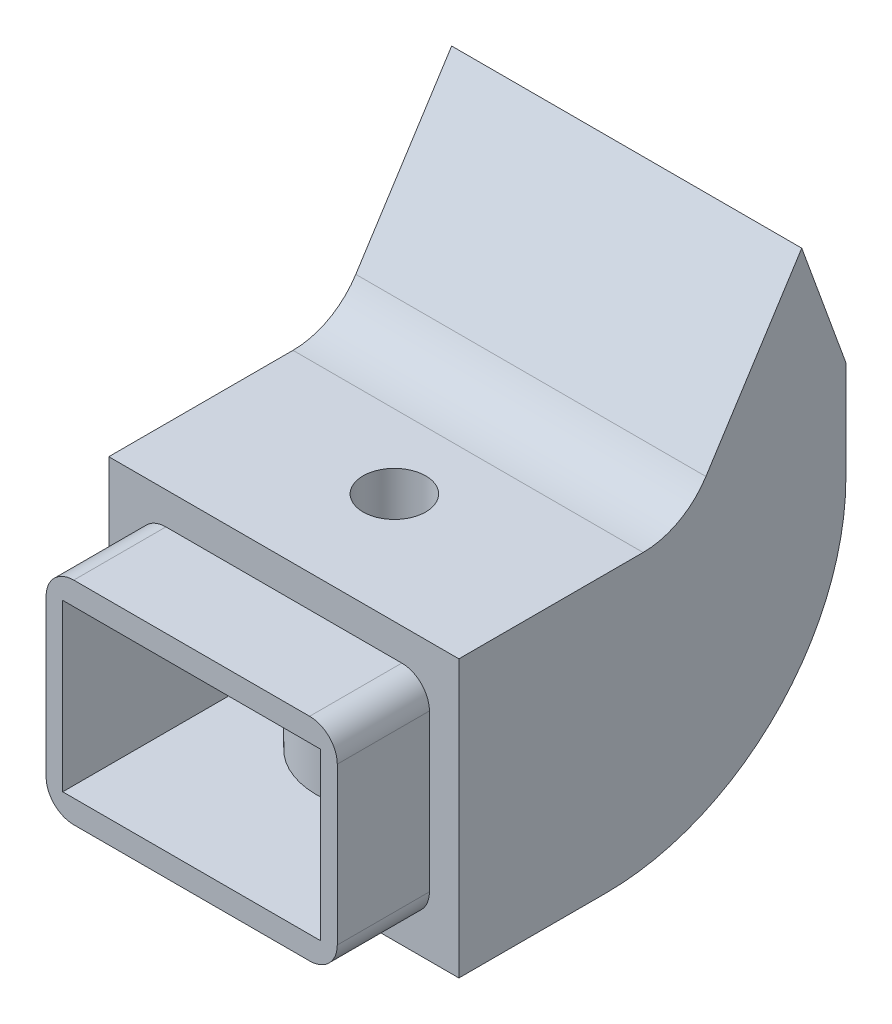
SolidWorks part; units mm, degrees
ref_plane "Alzado" through (0, 0, 0) normal (0, 0, 1) x (1, 0, 0)
ref_plane "Planta" through (0, 0, 0) normal (0, 1, 0) x (1, 0, 0)
ref_plane "Vista lateral" through (0, 0, 0) normal (1, 0, 0) x (0, 0, -1)
ref_plane "Plano1" through (7.9361, 0, 0) normal (1, 0, 0) x (0, 0, -1)
sketch "Croquis1" plane through (7.9361, 0, 0) normal (1, 0, 0) x (0, 0, -1)
  line L0 (-154.2857, -37.2136) -> (-128.2857, -37.2136)
  line L1 (-128.2857, -37.2136) -> (-128.2857, -33.7936)
  line L2 (-128.2857, -33.7936) -> (-137.0738, -9.6487)
  line L3 (-137.0738, -9.6487) -> (-149.2857, -9.6487)
  spline S0 degree 3 poles (-154.2857, -9.6487) (-152.6191, -9.6487) (-150.9524, -9.6487) (-149.2857, -9.6487) knots 0 0 0 0 1 1 1 1
  spline S1 degree 3 poles (-154.2857, -9.6487) (-154.2857, -18.837) (-154.2857, -28.0253) (-154.2857, -37.2136) knots 0 0 0 0 1 1 1 1
  dimension "D1" = 8.788
  dimension "D2" = 21
  dimension "D3" = 26
  dimension "D4" = 3.42
  dimension "D5" = 27.5649
extrude "Saliente-Extruir1" add sketch "Croquis1" against normal blind 18
sketch "Croquis2" plane through (0, -37.2136, 0) normal (0, -1, 0) x (1, 0, 0)
  line L0 (-10.0639, 154.2857) -> (7.9361, 154.2857)
  line L1 (7.9361, 149.2857) -> (7.9361, 128.2857)
  line L2 (7.9361, 128.2857) -> (-10.0639, 128.2857)
  line L3 (-10.0639, 128.2857) -> (-10.0639, 154.2857)
  line L4 (7.9361, 154.2857) -> (7.9361, 128.2857) construction
  spline S0 degree 3 poles (7.9361, 154.2857) (7.9361, 152.6191) (7.9361, 150.9524) (7.9361, 149.2857) knots 0 0 0 0 1 1 1 1
  dimension "D1" = 18
  dimension "D2" = 5
  dimension "D3" = 26
extrude "Saliente-Extruir2" add sketch "Croquis2" along normal blind 12
sketch "Croquis3" plane through (-10.0639, 0, 0) normal (-1, 0, 0) x (0, 0, 1)
  line L0 (135.0785, -49.2136) -> (137.8109, -49.2136)
  line L1 (137.8109, -49.2136) -> (137.8109, -40.2136)
  line L2 (137.8109, -40.2136) -> (130.2514, -28.3931)
  line L3 (130.2514, -28.3931) -> (129.3486, -30.8735)
  line L4 (129.3486, -30.8735) -> (135.0785, -49.2136)
  line L6 (137.0738, -9.6487) -> (149.2857, -9.6487) construction
  dimension "D1" = 16.4749
  dimension "D2" = 19.2073
  dimension "D3" = 24.0344
  dimension "D4" = 24.9371
  dimension "D5" = 18.7444
  dimension "D6" = 21.2248
  dimension "D7" = 30.5649
  dimension "D8" = 39.5649
extrude "Cortar-Extruir1" cut sketch "Croquis3" against normal blind 17
sketch "Croquis4" plane through (-10.0639, 0, 0) normal (-1, 0, 0) x (0, 0, 1)
  line L0 (137.8109, -49.2136) -> (154.2857, -49.2136)
  line L1 (154.2857, -49.2136) -> (154.2857, -40.2136)
  line L2 (154.2857, -40.2136) -> (137.8109, -40.2136)
  line L3 (137.8109, -40.2136) -> (137.8109, -49.2136)
  line L4 (154.2857, -49.2136) -> (137.8109, -49.2136) construction
  dimension "D1" = 16.4749
  dimension "D2" = 9
extrude "Cortar-Extruir2" cut sketch "Croquis4" against normal blind 15.5
sketch "Croquis5" plane through (0, 0, 154.2857) normal (0, 0, 1) x (1, 0, 0)
  line L0 (-10.0639, -40.2136) -> (-9.4639, -40.2136)
  line L1 (-9.4639, -40.2136) -> (-9.4639, -38.9636)
  line L2 (-9.4639, -38.9636) -> (6.3361, -38.9636)
  line L3 (6.3361, -38.9636) -> (6.3361, -49.2136)
  line L4 (6.3361, -49.2136) -> (7.9361, -49.2136)
  line L5 (7.9361, -49.2136) -> (7.9361, -37.2136)
  line L6 (7.9361, -9.6487) -> (-10.0639, -9.6487)
  line L7 (-10.0639, -37.2136) -> (-10.0639, -40.2136)
  line L8 (7.9361, -49.2136) -> (7.9361, -37.2136) construction
  line L9 (7.9361, -49.2136) -> (5.4361, -49.2136) construction
  spline S0 degree 3 poles (7.9361, -9.6487) (7.9361, -18.837) (7.9361, -28.0253) (7.9361, -37.2136) knots 0 0 0 0 1 1 1 1
  spline S1 degree 3 poles (-10.0639, -9.6487) (-10.0639, -18.837) (-10.0639, -28.0253) (-10.0639, -37.2136) knots 0 0 0 0 1 1 1 1
  dimension "D1" = 1.6
  dimension "D2" = 17.4
  dimension "D3" = 18
  dimension "D4" = 9
  dimension "D5" = 10.25
  dimension "D6" = 12
  dimension "D7" = 39.5649
extrude "Cortar-Extruir3" cut sketch "Croquis5" against normal blind 5
sketch "Croquis6" plane through (0, -9.6487, 0) normal (0, 1, 0) x (-1, 0, 0)
  line L0 (-7.9361, 137.0738) -> (10.0639, 137.0738)
  line L1 (10.0639, 137.0738) -> (10.0639, 149.2857)
  line L2 (10.0639, 149.2857) -> (-7.9361, 149.2857)
  line L3 (-7.9361, 149.2857) -> (-7.9361, 137.0738)
  line L4 (-7.9361, 137.0738) -> (-7.9361, 149.2857) construction
  line L5 (-7.9361, 149.2857) -> (10.0639, 149.2857) construction
  dimension "D1" = 18
  dimension "D2" = 12.212
extrude "Cortar-Extruir4" cut sketch "Croquis6" against normal blind 27.5649
sketch "Croquis7" plane through (0, -40.2136, 0) normal (0, -1, 0) x (1, 0, 0)
  line L0 (-9.4639, 154.2857) -> (-8.5639, 154.2857)
  line L1 (-8.5639, 154.2857) -> (-8.5639, 137.8109)
  line L2 (-8.5639, 137.8109) -> (-10.0639, 137.8109)
  line L3 (-10.0639, 137.8109) -> (-10.0639, 149.2857)
  line L4 (-10.0639, 149.2857) -> (-9.4639, 149.2857)
  line L5 (-9.4639, 149.2857) -> (-9.4639, 154.2857)
  line L6 (-9.4639, 149.2857) -> (-9.4639, 154.2857) construction
  line L7 (5.4361, 154.2857) -> (-9.4639, 154.2857) construction
  dimension "D1" = 0.9
  dimension "D2" = 0.6
  dimension "D3" = 5
  dimension "D4" = 16.4749
extrude "Saliente-Extruir3" add sketch "Croquis7" along normal blind 9
sketch "Croquis8" plane through (0, -49.2136, 0) normal (0, -1, 0) x (1, 0, 0)
  line L0 (-9.4639, 154.2857) -> (6.3361, 154.2857)
  line L1 (6.3361, 154.2857) -> (6.3361, 149.2857)
  line L2 (6.3361, 149.2857) -> (7.9361, 149.2857)
  line L3 (7.9361, 149.2857) -> (7.9361, 128.2857)
  line L4 (7.9361, 128.2857) -> (-10.0639, 128.2857)
  line L5 (-10.0639, 128.2857) -> (-10.0639, 149.2857)
  line L6 (-10.0639, 149.2857) -> (-9.4639, 149.2857)
  line L7 (-9.4639, 149.2857) -> (-9.4639, 154.2857)
  line L8 (5.4361, 137.8109) -> (5.4361, 154.2857) construction
  line L9 (6.9361, 137.8109) -> (5.4361, 137.8109) construction
  dimension "D1" = 0.9
  dimension "D2" = 2.5
  dimension "D3" = 14.9
  dimension "D4" = 15.5
  dimension "D5" = 11.4749
  dimension "D6" = 16.4749
  dimension "D7" = 9.5251
extrude "Saliente-Extruir4" add sketch "Croquis8" along normal blind 1.25
sketch "Croquis9" plane through (0, -50.4636, 0) normal (0, -1, 0) x (1, 0, 0)
  line L0 (-10.0639, 128.2857) -> (-10.0639, 149.2857)
  line L1 (-10.0639, 149.2857) -> (7.9361, 149.2857)
  line L2 (7.9361, 149.2857) -> (7.9361, 128.2857)
  line L3 (7.9361, 128.2857) -> (-10.0639, 128.2857)
  line L4 (-10.0639, 149.2857) -> (-10.0639, 128.2857) construction
  line L5 (-9.4639, 149.2857) -> (-10.0639, 149.2857) construction
  dimension "D1" = 18
  dimension "D2" = 21
extrude "Saliente-Extruir5" add sketch "Croquis9" along normal blind 1.75
sketch "Croquis10" plane through (0, 0, 137.8109) normal (0, 0, -1) x (-1, 0, 0)
  line L0 (-6.9361, -49.2136) -> (-5.4361, -49.2136)
  line L1 (-5.4361, -49.2136) -> (-5.4361, -40.2136)
  line L2 (-5.4361, -40.2136) -> (-6.9361, -40.2136)
  line L3 (-6.9361, -40.2136) -> (-6.9361, -49.2136)
  line L4 (-5.4361, -40.2136) -> (-5.4361, -49.2136) construction
  line L5 (-6.9361, -40.2136) -> (-5.4361, -40.2136) construction
  dimension "D1" = 1.5
  dimension "D2" = 9
extrude "Cortar-Extruir5" cut sketch "Croquis10" against normal blind 6.4749
sketch "Croquis11" plane through (0, 0, 137.8109) normal (0, 0, -1) x (-1, 0, 0)
  line L0 (8.5639, -49.2136) -> (10.0639, -49.2136)
  line L1 (10.0639, -49.2136) -> (10.0639, -40.2136)
  line L2 (10.0639, -40.2136) -> (8.5639, -40.2136)
  line L3 (8.5639, -40.2136) -> (8.5639, -49.2136)
  line L4 (8.5639, -49.2136) -> (8.5639, -40.2136) construction
  line L5 (10.0639, -40.2136) -> (8.5639, -40.2136) construction
  dimension "D1" = 1.5
  dimension "D2" = 9
extrude "Cortar-Extruir6" cut sketch "Croquis11" against normal blind 6.4749
sketch "Croquis12" plane through (-10.0639, 0, 0) normal (-1, 0, 0) x (0, 0, 1)
  line L0 (149.2857, -52.2136) -> (128.2857, -52.2136)
  line L1 (128.2857, -52.2136) -> (128.2857, -33.7936)
  line L2 (128.2857, -33.7936) -> (137.0738, -9.6487)
  line L3 (137.0738, -9.6487) -> (137.0738, -37.2136)
  line L4 (137.0738, -37.2136) -> (149.2857, -37.2136)
  line L5 (149.2857, -37.2136) -> (149.2857, -52.2136)
  line L7 (144.2857, -49.2136) -> (135.0785, -49.2136) construction
  dimension "D1" = 8.788
  dimension "D2" = 21
  dimension "D3" = 12
  dimension "D4" = 15.42
  dimension "D5" = 39.5649
  dimension "D6" = 3
extrude "Saliente-Extruir6" add sketch "Croquis12" along normal blind 1
draft "Ángulo de salida1" type of draft neutral plane draft angle 32.6 faces to draft 1 face at (-1.5639, -23.4312, 137.0738) neutral plane through (0, -37.2136, 0) neutral plane normal (0, 1, 0) parameters "D1"=32.6
ref_plane "Plano2" through (0, 0, 143.2857) normal (0, 0, -1) x (-1, 0, 0)
sketch "Croquis13" plane through (0, 0, 143.2857) normal (0, 0, -1) x (-1, 0, 0)
  line L0 (-2.6861, -49.2136) -> (1.5639, -49.2136)
  line L1 (1.5639, -49.2136) -> (1.5639, -40.2136)
  line L2 (1.5639, -40.2136) -> (-1.1361, -40.2136)
  line L3 (-1.1361, -40.2136) -> (-1.1361, -46.8136)
  line L4 (-1.1361, -46.8136) -> (-2.6861, -46.8136)
  line L5 (-2.6861, -46.8136) -> (-2.6861, -49.2136)
  line L6 (1.5639, -49.2136) -> (1.5639, -40.2136) construction
  dimension "D1" = 1.55
  dimension "D2" = 4.25
  dimension "D3" = 2.4
  dimension "D4" = 9
revolve "Revolución1" add sketch "Croquis13" angle 360 about L6 reverse direction yes
hole_wizard "Refrentado para tornillo con cabeza hexagonal de M31" positions "Croquis15" profile "Croquis14" counterbore size "M3" standard "Ansi Metric"
sketch "Croquis15" plane through (0, -52.2136, 0) normal (0, -1, 0) x (-1, 0, 0)
  point P0 (1.5639, -143.2857)
sketch "Croquis14" plane through (-1.5639, -52.2136, 143.2857) normal (1, 0, 0) x (0, 0, -1)
  line L0 (0, 0) -> (0, 24.9978)
  line L1 (0, 24.9978) -> (1.7, 24.9978)
  line L3 (1.7, 24.9978) -> (1.7, 3.4)
  line L4 (1.7, 3.4) -> (3.25, 3.4)
  line L5 (3.25, 3.4) -> (3.25, 0)
  line L7 (3.25, 0) -> (0, 0)
  line L11 (0, -6.35) -> (0, 107.95) construction
  dimension "Diámetro de taladro hasta el siguiente" = 3.4
  dimension "Profundidad de taladro hasta el siguiente" = 24.9978
  dimension "Diámetro de refrentado" = 6.5
  dimension "Profundidad de refrentado" = 3.4
fillet "Redondeo1" radius 1.5 4 edges at (6.3361, -38.9636, 151.7857) (-9.4639, -38.9636, 151.7857) tangent propagation no
fillet "Redondeo2" radius 4.0466 1 edges at (-1.5639, -37.2136, 137.0738) tangent propagation no
fillet "Redondeo3" radius 9.3945 1 edges at (-1.5639, -49.2136, 135.0785) tangent propagation no
fillet "Redondeo4" radius 10 1 edges at (-1.5639, -40.2136, 137.8109) tangent propagation no
fillet "Redondeo5" radius 13 1 edges at (-1.5639, -52.2136, 128.2857) tangent propagation no
